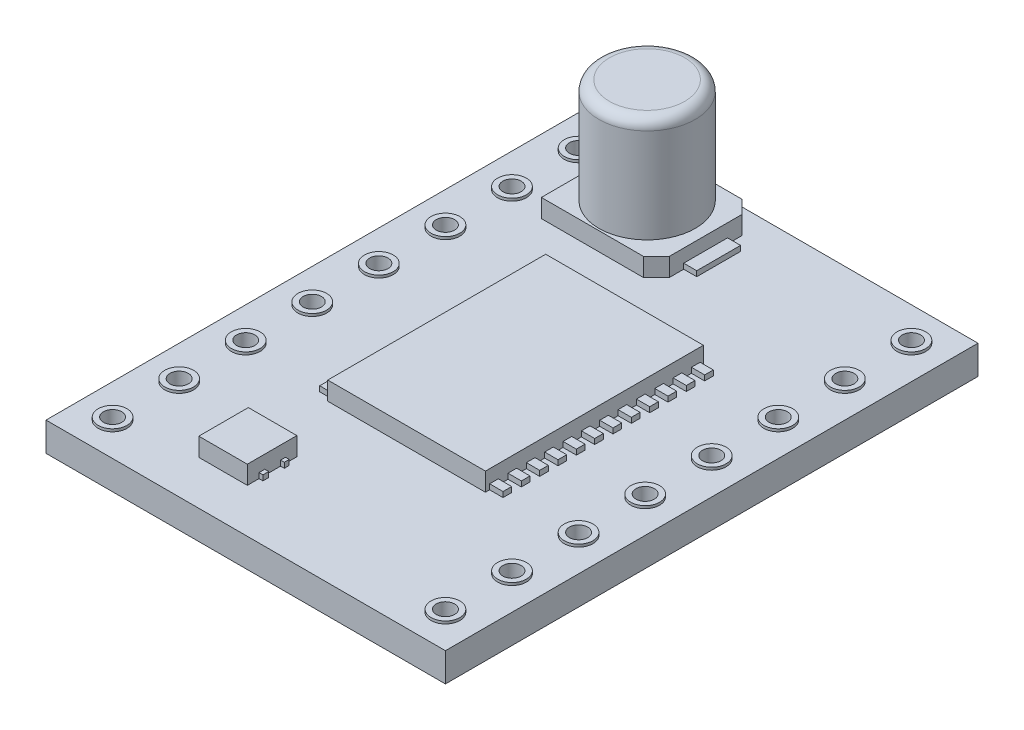
SolidWorks part; units mm, degrees
ref_plane "Plano frontal" through (0, 0, 0) normal (0, 0, 1) x (1, 0, 0)
ref_plane "Plano superior" through (0, 0, 0) normal (0, 1, 0) x (1, 0, 0)
ref_plane "Plano direito" through (0, 0, 0) normal (1, 0, 0) x (0, 0, -1)
sketch "Esboço1" plane through (0, 0, 0) normal (0, 1, 0) x (1, 0, 0)
  line L1 (-7.62, -10.16) -> (7.62, -10.16)
  line L2 (-7.62, -10.16) -> (-7.62, 10.16)
  line L3 (-7.62, 10.16) -> (7.62, 10.16)
  line L4 (7.62, -10.16) -> (7.62, 10.16)
  line L5 (-7.62, -10.16) -> (7.62, 10.16) construction
  line L6 (-7.62, 10.16) -> (7.62, -10.16) construction
  point P0 (0, 0)
  dimension "D1" = 15.24
  dimension "D2" = 20.32
extrude "Ressalto-extrusão1" add sketch "Esboço1" along normal blind 1.1
sketch "Esboço2" plane through (0, 1.1, 0) normal (0, 1, 0) x (1, 0, 0)
  line L0 (0, 10.16) -> (0, -10.16) construction
  line L1 (7.62, 10.16) -> (-7.62, 10.16) construction
  line L2 (-7.62, -10.16) -> (7.62, -10.16) construction
  line L3 (-6.35, 10.16) -> (-6.35, -10.16) construction
  line L4 (6.35, 1.27) -> (6.35, -1.27) construction
  line L5 (6.35, 0) -> (0, 0) construction
  circle A0 centre (-6.35, 8.89) radius 0.35
  circle A1 centre (-6.35, 6.35) radius 0.35
  circle A2 centre (-6.35, 3.81) radius 0.35
  circle A3 centre (-6.35, 1.27) radius 0.35
  circle A4 centre (-6.35, -1.27) radius 0.35
  circle A5 centre (-6.35, -3.81) radius 0.35
  circle A6 centre (-6.35, -6.35) radius 0.35
  circle A7 centre (-6.35, -8.89) radius 0.35
  circle A8 centre (6.35, -8.89) radius 0.35
  circle A9 centre (6.35, -6.35) radius 0.35
  circle A10 centre (6.35, -3.81) radius 0.35
  circle A11 centre (6.35, -1.27) radius 0.35
  circle A12 centre (6.35, 1.27) radius 0.35
  circle A13 centre (6.35, 3.81) radius 0.35
  circle A14 centre (6.35, 6.35) radius 0.35
  circle A15 centre (6.35, 8.89) radius 0.35
  dimension "D1" = 0.7
  dimension "D3" = 12.7
  dimension "D2" = 8
extrude "Corte-extrusão1" cut sketch "Esboço2" against normal through all
sketch "Esboço3" plane through (0, 1.1, -1.1) normal (0, -1, 0) x (1, 0, 0)
  line L0 (0, 11.26) -> (0, -9.06) construction
  line L3 (-6.35, 11.26) -> (-6.35, -9.06) construction
  line L4 (6.35, 2.37) -> (6.35, -0.17) construction
  line L5 (6.35, 1.1) -> (0, 1.1) construction
  line L6 (7.62, -9.06) -> (-7.62, -9.06) construction
  line L7 (-7.62, 11.26) -> (7.62, 11.26) construction
  circle A0 centre (-6.35, 9.99) radius 0.35
  circle A1 centre (-6.35, 7.45) radius 0.35
  circle A2 centre (-6.35, 4.91) radius 0.35
  circle A3 centre (-6.35, 2.37) radius 0.35
  circle A4 centre (-6.35, -0.17) radius 0.35
  circle A5 centre (-6.35, -2.71) radius 0.35
  circle A6 centre (-6.35, -5.25) radius 0.35
  circle A7 centre (-6.35, -7.79) radius 0.35
  circle A8 centre (6.35, -7.79) radius 0.35
  circle A9 centre (6.35, -5.25) radius 0.35
  circle A10 centre (6.35, -2.71) radius 0.35
  circle A11 centre (6.35, -0.17) radius 0.35
  circle A12 centre (6.35, 2.37) radius 0.35
  circle A13 centre (6.35, 4.91) radius 0.35
  circle A14 centre (6.35, 7.45) radius 0.35
  circle A15 centre (6.35, 9.99) radius 0.35
  circle A16 centre (-6.35, 9.99) radius 0.55
  circle A17 centre (-6.35, 7.45) radius 0.55
  circle A18 centre (-6.35, 4.91) radius 0.55
  circle A19 centre (-6.35, 2.37) radius 0.55
  circle A20 centre (-6.35, -0.17) radius 0.55
  circle A21 centre (-6.35, -2.71) radius 0.55
  circle A22 centre (-6.35, -5.25) radius 0.55
  circle A23 centre (-6.35, -7.79) radius 0.55
  circle A24 centre (6.35, -7.79) radius 0.55
  circle A25 centre (6.35, -5.25) radius 0.55
  circle A26 centre (6.35, -2.71) radius 0.55
  circle A27 centre (6.35, -0.17) radius 0.55
  circle A28 centre (6.35, 2.37) radius 0.55
  circle A29 centre (6.35, 4.91) radius 0.55
  circle A30 centre (6.35, 7.45) radius 0.55
  circle A31 centre (6.35, 9.99) radius 0.55
  dimension "D1" = 0.7
  dimension "D3" = 12.7
  dimension "D4" = 0.2
  dimension "D5" = 0.2
  dimension "D2" = 8
extrude "Ressalto-extrusão2" add sketch "Esboço3" along normal blind 1.2 and the other way blind 0.1
sketch "Esboço4" plane through (0, 1.1, 0) normal (0, 1, 0) x (1, 0, 0)
  line L0 (-0.9382, 5.9467) -> (-0.4382, 6.4467)
  line L1 (-2.8676, 4.1532) -> (3.1493, 4.1532)
  line L2 (-2.8676, 4.1532) -> (-2.8676, -4.1625)
  line L3 (-2.8676, -4.1625) -> (3.1493, -4.1625)
  line L4 (3.1493, 4.1532) -> (3.1493, -4.1625)
  line L5 (-4.8266, 9.7149) -> (-0.9382, 9.7149)
  line L6 (-4.8266, 9.7149) -> (-4.8266, 5.9467)
  line L7 (-4.8266, 5.9467) -> (-0.9382, 5.9467)
  line L8 (-0.4382, 9.2149) -> (-0.4382, 6.4467)
  line L9 (-0.9382, 9.7149) -> (-0.4382, 9.2149)
  line L11 (-3.4732, -6.5866) -> (-1.6217, -6.5866)
  line L12 (-3.4732, -6.5866) -> (-3.4732, -8.477)
  line L13 (-3.4732, -8.477) -> (-1.6217, -8.477)
  line L14 (-1.6217, -6.5866) -> (-1.6217, -8.477)
  line L15 (-3.4732, -6.5866) -> (-1.6217, -8.477) construction
  line L16 (-3.4732, -8.477) -> (-1.6217, -6.5866) construction
  point P5 (-0.4382, 5.9467)
  point P7 (-0.4382, 9.7149)
  point P12 (-2.5475, -7.5318)
extrude "Ressalto-extrusão3" add sketch "Esboço4" along normal blind 0.7
sketch "Esboço5" plane through (0, 1.8, 0) normal (0, 1, 0) x (1, 0, 0)
  circle A0 centre (-2.7044, 7.8592) radius 1.839
extrude "Ressalto-extrusão4" add sketch "Esboço5" along normal blind 4
sketch "Esboço6" plane through (0, 1.1, 0) normal (0, 1, 0) x (1, 0, 0)
  line L0 (-3.3386, 3.3248) -> (-3.3386, 2.9947)
  line L1 (-3.3392, 4.0248) -> (-2.3996, 4.0248)
  line L2 (-3.3392, 4.0248) -> (-3.3392, 3.6947)
  line L3 (-3.3392, 3.6947) -> (-2.3996, 3.6947)
  line L4 (-2.3996, 4.0248) -> (-2.3996, 3.6947)
  line L5 (-3.3386, 3.3248) -> (-2.399, 3.3248)
  line L6 (-2.399, 3.3248) -> (-2.399, 2.9947)
  line L7 (-3.3386, 2.9947) -> (-2.399, 2.9947)
  line L8 (-3.3379, 2.6248) -> (-3.3379, 2.2947)
  line L9 (-3.3379, 2.6248) -> (-2.3984, 2.6248)
  line L10 (-2.3984, 2.6248) -> (-2.3984, 2.2947)
  line L11 (-3.3379, 2.2947) -> (-2.3984, 2.2947)
  line L12 (-3.3373, 1.9248) -> (-3.3373, 1.5947)
  line L13 (-3.3373, 1.9248) -> (-2.3978, 1.9248)
  line L14 (-2.3978, 1.9248) -> (-2.3978, 1.5947)
  line L15 (-3.3373, 1.5947) -> (-2.3978, 1.5947)
  line L16 (-3.3367, 1.2248) -> (-3.3367, 0.8947)
  line L17 (-3.3367, 1.2248) -> (-2.3971, 1.2248)
  line L18 (-2.3971, 1.2248) -> (-2.3971, 0.8947)
  line L19 (-3.3367, 0.8947) -> (-2.3971, 0.8947)
  line L20 (-3.336, 0.5248) -> (-3.336, 0.1947)
  line L21 (-3.336, 0.5248) -> (-2.3965, 0.5248)
  line L22 (-2.3965, 0.5248) -> (-2.3965, 0.1947)
  line L23 (-3.336, 0.1947) -> (-2.3965, 0.1947)
  line L24 (-3.3354, -0.1752) -> (-3.3354, -0.5053)
  line L25 (-3.3354, -0.1752) -> (-2.3959, -0.1752)
  line L26 (-2.3959, -0.1752) -> (-2.3959, -0.5053)
  line L27 (-3.3354, -0.5053) -> (-2.3959, -0.5053)
  line L28 (-3.3348, -0.8752) -> (-3.3348, -1.2053)
  line L29 (-3.3348, -0.8752) -> (-2.3952, -0.8752)
  line L30 (-2.3952, -0.8752) -> (-2.3952, -1.2053)
  line L31 (-3.3348, -1.2053) -> (-2.3952, -1.2053)
  line L32 (-3.3341, -1.5752) -> (-3.3341, -1.9053)
  line L33 (-3.3341, -1.5752) -> (-2.3946, -1.5752)
  line L34 (-2.3946, -1.5752) -> (-2.3946, -1.9053)
  line L35 (-3.3341, -1.9053) -> (-2.3946, -1.9053)
  line L36 (-3.3335, -2.2752) -> (-3.3335, -2.6053)
  line L37 (-3.3335, -2.2752) -> (-2.394, -2.2752)
  line L38 (-2.394, -2.2752) -> (-2.394, -2.6053)
  line L39 (-3.3335, -2.6053) -> (-2.394, -2.6053)
  line L40 (-3.3329, -2.9752) -> (-3.3329, -3.3053)
  line L41 (-3.3329, -2.9752) -> (-2.3933, -2.9752)
  line L42 (-2.3933, -2.9752) -> (-2.3933, -3.3053)
  line L43 (-3.3329, -3.3053) -> (-2.3933, -3.3053)
  line L44 (-3.3323, -3.6752) -> (-3.3323, -4.0053)
  line L45 (-3.3323, -3.6752) -> (-2.3927, -3.6752)
  line L46 (-2.3927, -3.6752) -> (-2.3927, -4.0053)
  line L47 (-3.3323, -4.0053) -> (-2.3927, -4.0053)
  line L48 (2.7142, 3.3278) -> (2.7142, 2.9976)
  line L49 (2.7136, 4.0278) -> (3.6531, 4.0278)
  line L50 (2.7136, 4.0278) -> (2.7136, 3.6976)
  line L51 (2.7136, 3.6976) -> (3.6531, 3.6976)
  line L52 (3.6531, 4.0278) -> (3.6531, 3.6976)
  line L53 (2.7142, 3.3278) -> (3.6538, 3.3278)
  line L54 (3.6538, 3.3278) -> (3.6538, 2.9976)
  line L55 (2.7142, 2.9976) -> (3.6538, 2.9976)
  line L56 (2.7149, 2.6278) -> (2.7149, 2.2976)
  line L57 (2.7149, 2.6278) -> (3.6544, 2.6278)
  line L58 (3.6544, 2.6278) -> (3.6544, 2.2976)
  line L59 (2.7149, 2.2976) -> (3.6544, 2.2976)
  line L60 (2.7155, 1.9278) -> (2.7155, 1.5976)
  line L61 (2.7155, 1.9278) -> (3.655, 1.9278)
  line L62 (3.655, 1.9278) -> (3.655, 1.5976)
  line L63 (2.7155, 1.5976) -> (3.655, 1.5976)
  line L64 (2.7161, 1.2278) -> (2.7161, 0.8976)
  line L65 (2.7161, 1.2278) -> (3.6557, 1.2278)
  line L66 (3.6557, 1.2278) -> (3.6557, 0.8976)
  line L67 (2.7161, 0.8976) -> (3.6557, 0.8976)
  line L68 (2.7167, 0.5278) -> (2.7167, 0.1976)
  line L69 (2.7167, 0.5278) -> (3.6563, 0.5278)
  line L70 (3.6563, 0.5278) -> (3.6563, 0.1976)
  line L71 (2.7167, 0.1976) -> (3.6563, 0.1976)
  line L72 (2.7174, -0.1722) -> (2.7174, -0.5024)
  line L73 (2.7174, -0.1722) -> (3.6569, -0.1722)
  line L74 (3.6569, -0.1722) -> (3.6569, -0.5024)
  line L75 (2.7174, -0.5024) -> (3.6569, -0.5024)
  line L76 (2.718, -0.8722) -> (2.718, -1.2024)
  line L77 (2.718, -0.8722) -> (3.6576, -0.8722)
  line L78 (3.6576, -0.8722) -> (3.6576, -1.2024)
  line L79 (2.718, -1.2024) -> (3.6576, -1.2024)
  line L80 (2.7186, -1.5722) -> (2.7186, -1.9024)
  line L81 (2.7186, -1.5722) -> (3.6582, -1.5722)
  line L82 (3.6582, -1.5722) -> (3.6582, -1.9024)
  line L83 (2.7186, -1.9024) -> (3.6582, -1.9024)
  line L84 (2.7193, -2.2722) -> (2.7193, -2.6024)
  line L85 (2.7193, -2.2722) -> (3.6588, -2.2722)
  line L86 (3.6588, -2.2722) -> (3.6588, -2.6024)
  line L87 (2.7193, -2.6024) -> (3.6588, -2.6024)
  line L88 (2.7199, -2.9722) -> (2.7199, -3.3024)
  line L89 (2.7199, -2.9722) -> (3.6594, -2.9722)
  line L90 (3.6594, -2.9722) -> (3.6594, -3.3024)
  line L91 (2.7199, -3.3024) -> (3.6594, -3.3024)
  line L92 (2.7205, -3.6722) -> (2.7205, -4.0024)
  line L93 (2.7205, -3.6722) -> (3.6601, -3.6722)
  line L94 (3.6601, -3.6722) -> (3.6601, -4.0024)
  line L95 (2.7205, -4.0024) -> (3.6601, -4.0024)
  line L96 (-3.5952, -7.8113) -> (-3.5952, -8.031)
  line L97 (-3.6359, -7.0212) -> (-1.4795, -7.0212)
  line L98 (-3.6359, -7.0212) -> (-3.6359, -7.2091)
  line L99 (-3.6359, -7.2091) -> (-1.4795, -7.2091)
  line L100 (-1.4795, -7.0212) -> (-1.4795, -7.2091)
  line L101 (-3.5952, -7.8113) -> (-1.4713, -7.8113)
  line L102 (-1.4713, -7.8113) -> (-1.4713, -8.031)
  line L103 (-3.5952, -8.031) -> (-1.4713, -8.031)
  line L105 (-5.2715, 8.6625) -> (0.0584, 8.6625)
  line L106 (-5.2715, 8.6625) -> (-5.2715, 6.9896)
  line L107 (-5.2715, 6.9896) -> (0.0584, 6.9896)
  line L108 (0.0584, 8.6625) -> (0.0584, 6.9896)
  dimension "D1" = 12
extrude "Ressalto-extrusão5" add sketch "Esboço6" along normal blind 0.2
fillet "Filete1" radius 0.4 1 edges at (-2.7044, 5.8, -6.0201)
